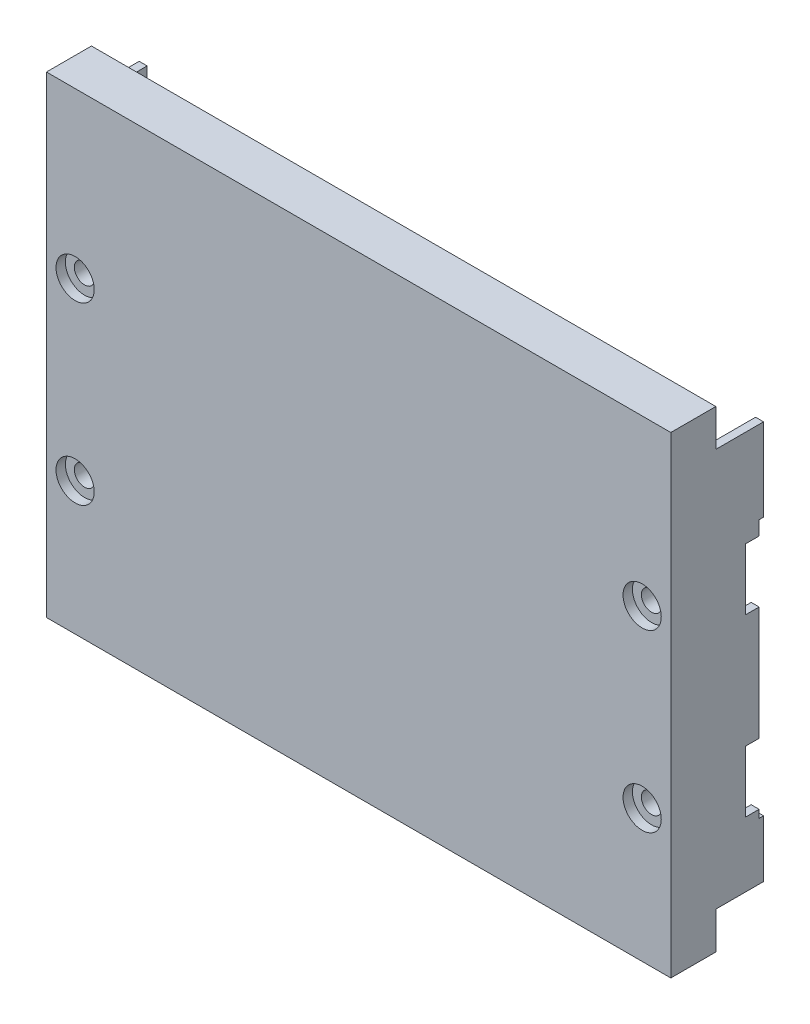
SolidWorks part; units mm, degrees
ref_plane "Front Plane" through (0, 0, 0) normal (0, 0, 1) x (1, 0, 0)
ref_plane "Top Plane" through (0, 0, 0) normal (0, 1, 0) x (1, 0, 0)
ref_plane "Right Plane" through (0, 0, 0) normal (1, 0, 0) x (0, 0, -1)
sketch "Sketch1" plane through (0, 0, 0) normal (0, 0, 1) x (1, 0, 0)
  line L0 (-30.5002, 35.0258) -> (66.0198, 35.0258) construction
  line L1 (67.5438, 35.0258) -> (-32.0242, 35.0258)
  line L2 (67.5438, 35.0258) -> (67.5438, -28.4742)
  line L3 (67.5438, -28.4742) -> (-32.0242, -28.4742)
  line L4 (-32.0242, 35.0258) -> (-32.0242, -28.4742)
  line L5 (66.0198, -28.4742) -> (-30.5002, -28.4742) construction
  line L7 (66.0198, 35.0258) -> (66.0198, -28.4742) construction
  line L8 (-30.5002, -28.4742) -> (-30.5002, 35.0258) construction
  dimension "D1" = 1.524
  dimension "D2" = 1.524
extrude "base" add sketch "Sketch1" along normal blind 5.08
sketch "Sketch2" plane through (0, 0, 0) normal (0, 0, -1) x (-1, 0, 0)
  line L0 (-67.5438, 35.0258) -> (32.0242, 35.0258) construction
  line L1 (30.5002, -26.9502) -> (-66.0198, -26.9502)
  line L2 (30.5002, -26.9502) -> (30.5002, 33.5018)
  line L3 (30.5002, 33.5018) -> (-66.0198, 33.5018)
  line L4 (-66.0198, -26.9502) -> (-66.0198, 33.5018)
  line L5 (-67.5438, -28.4742) -> (-67.5438, 35.0258) construction
  line L6 (32.0242, -28.4742) -> (-67.5438, -28.4742) construction
  line L7 (32.0242, 35.0258) -> (32.0242, -28.4742) construction
  dimension "D1" = 1.524
  dimension "D2" = 1.524
  dimension "D3" = 1.524
  dimension "D4" = 1.524
extrude "hollow" cut sketch "Sketch2" against normal blind 2
sketch "Sketch3" plane through (0, 0, 0) normal (0, 0, -1) x (-1, 0, 0)
  line L0 (-67.5438, 35.0258) -> (32.0242, 35.0258) construction
  line L1 (30.7542, 35.0258) -> (32.0242, 35.0258)
  line L2 (30.7542, 35.0258) -> (30.7542, -28.4742)
  line L3 (30.7542, -28.4742) -> (32.0242, -28.4742)
  line L4 (32.0242, 35.0258) -> (32.0242, -28.4742)
  line L5 (32.0242, -28.4742) -> (-67.5438, -28.4742) construction
  line L7 (32.0242, 35.0258) -> (32.0242, -28.4742) construction
  line L9 (-67.5438, 35.0258) -> (-66.2738, 35.0258)
  line L10 (-67.5438, 35.0258) -> (-67.5438, -28.4742)
  line L11 (-67.5438, -28.4742) -> (-66.2738, -28.4742)
  line L12 (-66.2738, 35.0258) -> (-66.2738, -28.4742)
  dimension "D1" = 1.27
  dimension "D2" = 1.27
extrude "end pieces" add sketch "Sketch3" along normal blind 9
sketch "Sketch7" plane through (67.5438, 0, 0) normal (1, 0, 0) x (0, 0, -1)
  line L0 (9, 35.0258) -> (9, -28.4742) construction
  line L1 (6.7986, 9.8068) -> (9, 9.8068)
  line L2 (6.7986, 9.8068) -> (6.7986, 19.6048)
  line L3 (6.7986, 19.6048) -> (9, 19.6048)
  line L4 (9, 9.8068) -> (9, 19.6048)
  line L5 (6.9986, 19.4048) -> (16.7986, 19.4048) construction
  line L6 (6.9986, 19.4048) -> (6.9986, 10.0068) construction
  line L7 (6.9986, 10.0068) -> (16.7986, 10.0068) construction
  line L8 (6.9986, -17.9332) -> (16.7986, -17.9332) construction
  line L9 (6.7986, -18.1332) -> (9, -18.1332)
  line L10 (6.7986, -18.1332) -> (6.7986, -8.3352)
  line L11 (6.7986, -8.3352) -> (9, -8.3352)
  line L12 (9, -18.1332) -> (9, -8.3352)
  dimension "D1" = 0.2
  dimension "D2" = 0.2
  dimension "D3" = 0.2
  dimension "D4" = 0.2
extrude "where top intrudes" cut sketch "Sketch7" against normal through all
sketch "cable stop wings alt" plane through (0, 0, 5.08) normal (0, 0, 1) x (1, 0, 0)
  line L1 (-32.0242, -28.4742) -> (67.5438, -28.4742)
  line L2 (-32.0242, -28.4742) -> (-32.0242, -33.4742)
  line L3 (-32.0242, -33.4742) -> (67.5438, -33.4742)
  line L4 (67.5438, -28.4742) -> (67.5438, -33.4742)
  line L5 (67.5438, 35.0258) -> (-32.0242, 35.0258) construction
  line L6 (-32.0242, -28.4742) -> (67.5438, -28.4742) construction
  line L8 (-32.0242, 35.0258) -> (67.5438, 35.0258)
  line L9 (-32.0242, 35.0258) -> (-32.0242, 40.0258)
  line L10 (-32.0242, 40.0258) -> (67.5438, 40.0258)
  line L11 (67.5438, 35.0258) -> (67.5438, 40.0258)
  line L12 (67.5438, -28.4742) -> (67.5438, 35.0258) construction
  line L13 (-32.0242, 35.0258) -> (-32.0242, -28.4742) construction
  dimension "D1" = 5
extrude "cable stop wing boss alt" add sketch "cable stop wings alt" against normal blind 1.5
sketch "Sketch4" plane through (0, 0, 2) normal (0, 0, -1) x (-1, 0, 0)
  circle A0 centre (-62.9718, 14.7058) radius 3.175
  circle A1 centre (-62.9718, -13.2342) radius 3.175
  circle A2 centre (27.4522, -13.2342) radius 3.175
  circle A4 centre (27.4522, 14.7058) radius 3.175
  dimension "D1" = 6.35
extrude "screw bosses" add sketch "Sketch4" along normal up to surface (2 mm away) up to face at (17.7598, 3.2758, 0)
sketch "Sketch5" plane through (0, 0, 0) normal (0, 0, -1) x (-1, 0, 0)
  circle A0 centre (-62.9718, 14.7058) radius 1.6256
  circle A1 centre (-62.9718, -13.2342) radius 1.6256
  circle A2 centre (27.4522, 14.7058) radius 1.6256
  circle A3 centre (27.4522, -13.2342) radius 1.6256
  dimension "D1" = 3.2512
extrude "screw holes" cut sketch "Sketch5" against normal through all
sketch "Sketch6" plane through (0, 0, 5.08) normal (0, 0, 1) x (1, 0, 0)
  circle A0 centre (62.9718, -13.2342) radius 3.048
  circle A1 centre (62.9718, 14.7058) radius 3.048
  circle A2 centre (-27.4522, -13.2342) radius 3.048
  circle A4 centre (-27.4522, 14.7058) radius 3.048
extrude "counter sink" cut sketch "Sketch6" against normal blind 1.5
sketch "Sketch25" plane through (0, 0, 5.08) normal (0, 0, 1) x (1, 0, 0)
  line L1 (-32.0242, 40.9458) -> (67.5438, 40.9458)
  line L2 (-32.0242, 40.9458) -> (-32.0242, 36.4458)
  line L3 (-32.0242, 36.4458) -> (67.5438, 36.4458)
  line L4 (67.5438, 40.9458) -> (67.5438, 36.4458)
  line L5 (-28.1176, 35.9458) -> (-26.1364, 35.9458) construction
  line L6 (-26.5479, -29.3942) -> (-28.5291, -29.3942) construction
  line L7 (67.5438, -34.3942) -> (-32.0242, -34.3942)
  line L8 (67.5438, -34.3942) -> (67.5438, -29.8942)
  line L9 (67.5438, -29.8942) -> (-32.0242, -29.8942)
  line L10 (-32.0242, -34.3942) -> (-32.0242, -29.8942)
  line L13 (-32.0242, 40.0258) -> (-32.0242, -33.4742) construction
  line L14 (67.5438, -33.4742) -> (67.5438, 40.0258) construction
  dimension "D1" = 0.5
  dimension "D2" = 5
  dimension "D3" = 0.5
  dimension "D4" = 5
extrude "box under connectors" add sketch "Sketch25" against normal offset from surface (7.1786 mm away) 3.81
sketch "Sketch26" plane through (-32.0242, 0, 0) normal (-1, 0, 0) x (0, 0, 1)
  line L0 (-2.0986, 40.9458) -> (5.08, 40.9458) construction
  line L1 (-2.0986, -34.3942) -> (5.08, -34.3942)
  line L2 (-2.0986, -34.3942) -> (-2.0986, 40.9458)
  line L3 (-2.0986, 40.9458) -> (5.08, 40.9458)
  line L4 (5.08, -34.3942) -> (5.08, 40.9458)
  line L5 (-2.0986, -34.3942) -> (5.08, -34.3942) construction
extrude "Fill ends" add sketch "Sketch26" against normal blind 1.5
extrude "Fill the other end" add sketch "Sketch26<2>" along normal blind 1.5 from surface starting at face at (67.5438, 2.2598, -3.2554)
sketch "Sketch26<2>" plane through (-32.0242, 0, 0) normal (-1, 0, 0) x (0, 0, 1) same geometry as "Sketch26"
sketch "Sketch27" plane through (-32.0242, 0, 0) normal (-1, 0, 0) x (0, 0, 1)
  line L0 (-10.2086, -28.4742) -> (-10.2086, -18.8862) construction
  line L1 (-9, -28.4742) -> (-9.7086, -28.4742)
  line L2 (-9, -28.4742) -> (-9, -19.3862)
  line L3 (-9, -19.3862) -> (-9.7086, -19.3862)
  line L4 (-9.7086, -28.4742) -> (-9.7086, -19.3862)
  line L5 (-9, -18.8862) -> (-10.2086, -18.8862) construction
  line L6 (-9, 21.3568) -> (-10.2086, 21.3568) construction
  line L7 (-9, 35.0258) -> (-9.7086, 35.0258)
  line L8 (-9, 35.0258) -> (-9, 21.8568)
  line L9 (-9, 21.8568) -> (-9.7086, 21.8568)
  line L10 (-9.7086, 35.0258) -> (-9.7086, 21.8568)
  line L11 (-10.2086, 21.3568) -> (-10.2086, 35.0258) construction
  dimension "D1" = 0.5
  dimension "D2" = 0.5
  dimension "D3" = 0.5
  dimension "D4" = 0.5
extrude "Boss-Extrude4" add sketch "Sketch27" against normal up to vertex (1.27 mm away) up to point (-30.7542, 35.0258, -9)
extrude "Boss-Extrude5" add sketch "Sketch27<2>" along normal up to vertex (-98.298 mm away) from surface up to point (66.2738, 35.0258, -9) starting at face at (67.5438, 2.0058, -4.9643)
sketch "Sketch27<2>" plane through (-32.0242, 0, 0) normal (-1, 0, 0) x (0, 0, 1) same geometry as "Sketch27"
